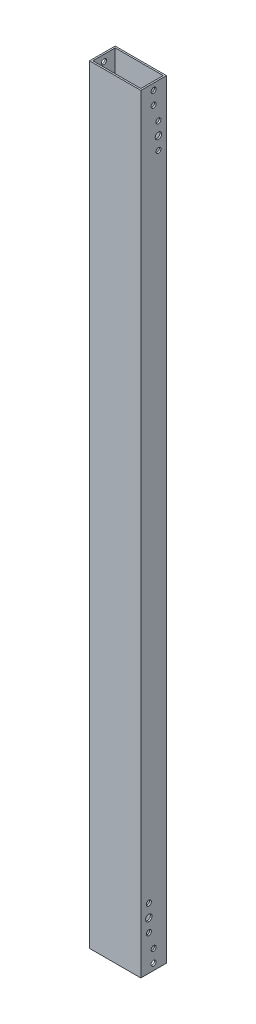
SolidWorks part; units mm, degrees
ref_plane "Front Plane" through (0, 0, 0) normal (0, 0, 1) x (1, 0, 0)
ref_plane "Top Plane" through (0, 0, 0) normal (0, 1, 0) x (1, 0, 0)
ref_plane "Right Plane" through (0, 0, 0) normal (1, 0, 0) x (0, 0, -1)
sketch "Sketch1" plane through (0, 0, 0) normal (0, 0, 1) x (1, 0, 0)
  line L1 (-25.4, -381) -> (25.4, -381)
  line L2 (-25.4, -381) -> (-25.4, 381)
  line L3 (-25.4, 381) -> (25.4, 381)
  line L4 (25.4, -381) -> (25.4, 381)
  line L5 (-25.4, -381) -> (25.4, 381) construction
  line L6 (-25.4, 381) -> (25.4, -381) construction
  point P0 (0, 0)
  dimension "D1" = 50.8
  dimension "D2" = 762
extrude "Boss-Extrude1" add sketch "Sketch1" along normal mid plane 25.4
shell "Shell1" thickness 1.5875 removed face at (0, -381, 0) removed face at (0, 381, 0)
sketch "Sketch3" plane through (0, 0, 0) normal (1, 0, 0) x (0, 0, -1)
  line L0 (-12.7, -381) -> (12.7, -381) construction
  circle A0 centre (0, -374.65) radius 2.4892
  circle A1 centre (0, -361.95) radius 2.4892
  point P6 (0, -381)
  dimension "D1" = 4.9784
  dimension "D2" = 6.35
  dimension "D3" = 12.7
extrude "Cut-Extrude1" cut sketch "Sketch3" against normal through all both and the other way through all
sketch "Sketch4" plane through (0, 0, 0) normal (1, 0, 0) x (0, 0, -1)
  line L0 (12.7, 381) -> (12.7, -381) construction
  line L3 (-12.7, 381) -> (12.7, 381) construction
  line L4 (-12.7, -381) -> (12.7, -381) construction
  line L5 (-12.7, 381) -> (-12.7, -381) construction
  circle A0 centre (4.7625, 333.375) radius 3.175
  circle A1 centre (4.7625, 346.075) radius 2.4892
  circle A2 centre (4.7625, 320.675) radius 2.4892
  circle A3 centre (-4.7625, -333.375) radius 3.175
  circle A4 centre (-4.7625, -320.675) radius 2.4892
  circle A5 centre (-4.7625, -346.075) radius 2.4892
  point P16 (-7.9085, -337.088)
  dimension "D1" = 6.35
  dimension "D4" = 4.9784
  dimension "D7" = 6.35
  dimension "D8" = 4.9784
  dimension "D2" = 7.9375
  dimension "D5" = 12.7
  dimension "D6" = 12.7
  dimension "D3" = 47.625
  dimension "D9" = 12.7
  dimension "D10" = 12.7
  dimension "D11" = 47.625
  dimension "D12" = 7.9375
extrude "Cut-Extrude2" cut sketch "Sketch4" against normal through all both and the other way through all
mirror "Mirror1" about plane through (0, 0, 0) normal (0, 1, 0) of "Cut-Extrude1"
equation "\"D6@Sketch4\"=\"D5@Sketch4\""
